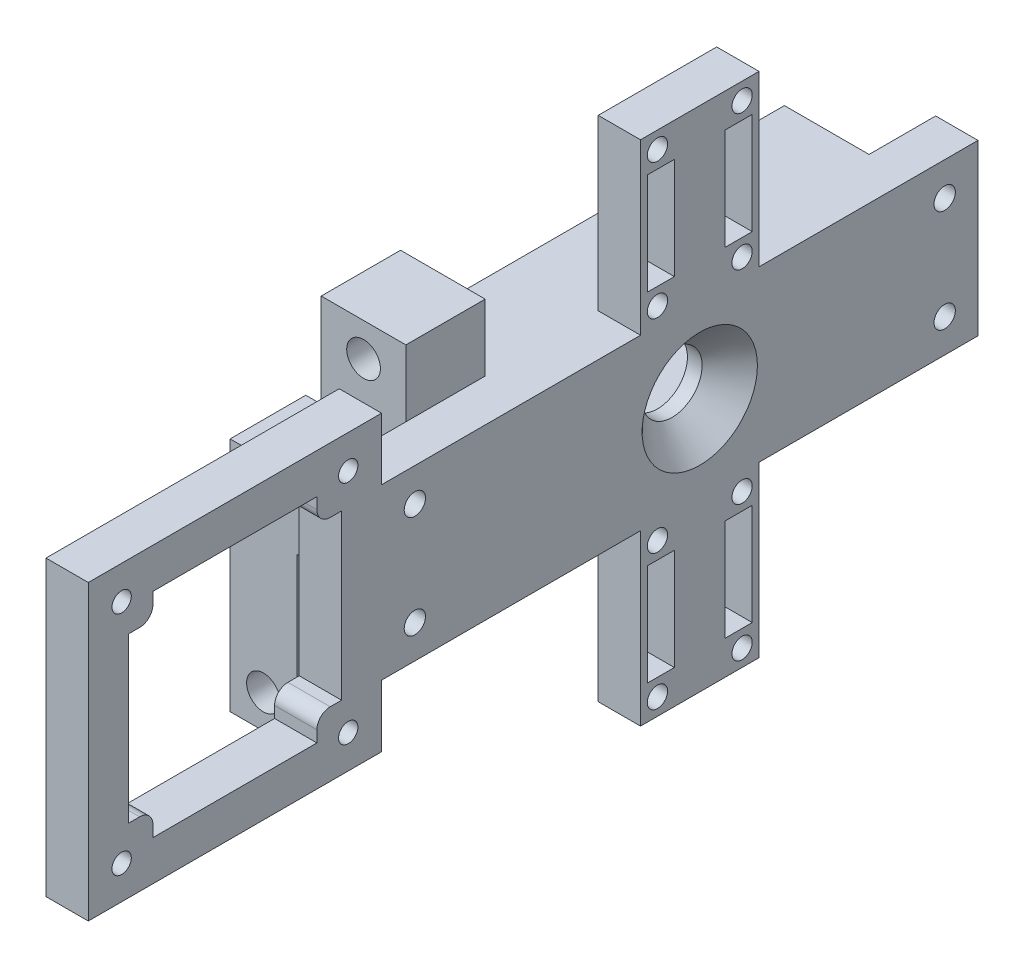
SolidWorks part; units mm, degrees
ref_plane "Front Plane" through (0, 0, 0) normal (0, 0, 1) x (1, 0, 0)
ref_plane "Top Plane" through (0, 0, 0) normal (0, 1, 0) x (1, 0, 0)
ref_plane "Right Plane" through (0, 0, 0) normal (1, 0, 0) x (0, 0, -1)
sketch "Sketch1" plane through (0, 0, 0) normal (0, 1, 0) x (1, 0, 0)
  line L1 (0, 0) -> (6.35, 0)
  line L2 (0, 0) -> (0, 89.5)
  line L3 (0, 89.5) -> (6.35, 89.5)
  line L4 (6.35, 0) -> (6.35, 89.5)
  dimension "D1" = 89.5
  dimension "D2" = 6.35
extrude "Boss-Extrude1" add sketch "Sketch1" along normal blind 25.4
sketch "Sketch2" plane through (0, 0, 0) normal (-1, 0, 0) x (0, 0, 1)
  line L0 (-89.5, 25.4) -> (0, 25.4) construction
  line L1 (-74.15, 20.05) -> (-21.35, 20.05)
  line L2 (-74.15, 20.05) -> (-74.15, 5.35)
  line L3 (-74.15, 5.35) -> (-21.35, 5.35)
  line L4 (-21.35, 20.05) -> (-21.35, 5.35)
  line L6 (-89.5, 25.4) -> (-89.5, 0) construction
  line L13 (-89.5, 0) -> (0, 0) construction
  line L14 (-79.5, 25.4) -> (-10, 25.4)
  line L15 (-79.5, 25.4) -> (-79.5, 0)
  line L16 (-79.5, 0) -> (-10, 0)
  line L17 (-10, 25.4) -> (-10, 0)
  line L18 (0, 25.4) -> (0, 0) construction
  dimension "D1" = 52.8
  dimension "D2" = 14.7
  dimension "D3" = 5.35
  dimension "D4" = 15.35
  dimension "D5" = 10
  dimension "D6" = 10
sketch "Sketch4" plane through (6.35, 0, 0) normal (1, 0, 0) x (0, 0, -1)
  line L0 (0, 25.4) -> (0, 0) construction
  line L1 (0, 34.7) -> (-44, 34.7)
  line L2 (0, 34.7) -> (0, -9.3)
  line L3 (0, -9.3) -> (-44, -9.3)
  line L4 (-44, 34.7) -> (-44, -9.3)
  line L6 (0, 25.4) -> (89.5, 25.4) construction
  circle A0 centre (-39, 29.7) radius 1.45
  circle A1 centre (-5, 29.7) radius 1.45
  circle A2 centre (-39, -4.3) radius 1.45
  circle A3 centre (-5, -4.3) radius 1.45
  dimension "D4" = 34
  dimension "D6" = 2.9
  dimension "D7" = 34
  dimension "D1" = 44
  dimension "D2" = 9.3
  dimension "D3" = 44
  dimension "D5" = 5
  dimension "D8" = 5
extrude "Boss-Extrude2" add sketch "Sketch4" against normal up to surface (6.35 mm away) up to face at (0, 12.7, -44.75)
hole_wizard "CSK for M8 Flat Head Machine Screw1" positions "Sketch6" profile "Sketch7" countersink size "M8" standard "ANSI Metric"
sketch "Sketch6" plane through (6.35, 0, 0) normal (1, 0, 0) x (0, 0, -1)
  line L1 (89.5, 25.4) -> (89.5, 0) construction
  line L2 (0, 25.4) -> (89.5, 25.4) construction
  point P0 (47.75, 12.7)
  dimension "D1" = 41.75
  dimension "D2" = 12.7
sketch "Sketch7" plane through (6.35, 12.7, -47.75) normal (0, 1, 0) x (0, 0, -1)
  line L0 (0, 0) -> (0, 20.2039)
  line L1 (0, 20.2039) -> (4.5, 17.5)
  line L2 (4.5, 17.5) -> (4.5, 4.15)
  line L3 (4.5, 4.15) -> (8.65, 0)
  line L5 (8.65, 0) -> (0, 0)
  line L6 (-4.5, 4.15) -> (-8.65, 0) construction
  line L10 (0, 20.2039) -> (-4.5, 17.5) construction
  line L11 (0, -6.35) -> (0, 107.95) construction
  dimension "Hole Dia." = 9
  dimension "Hole Depth" = 17.5
  dimension "Near C'Sink Dia." = 17.3
  dimension "Near C'Sink Angle" = 90
  dimension "Drill Angle" = 118
extrude "Boss-Extrude3" add sketch "Sketch2" along normal blind 12.7
sketch "Sketch9" plane through (0, 0, 0) normal (-1, 0, 0) x (0, 0, 1)
  line L1 (0, 34.7) -> (0, 25.4) construction
  line L2 (-10, 25.4) -> (0, 25.4) construction
  line L3 (-10, 0) -> (0, 0) construction
  line L4 (-89.5, 25.4) -> (-89.5, 0) construction
  circle A0 centre (-5, 20.4) radius 1.6
  circle A1 centre (-5, 5) radius 1.6
  circle A3 centre (-84.5, 5) radius 1.6
  circle A4 centre (-84.5, 20.4) radius 1.6
  dimension "D1" = 3.2
  dimension "D2" = 5
  dimension "D3" = 5
  dimension "D4" = 5
  dimension "D5" = 5
extrude "Cut-Extrude1" cut sketch "Sketch9" against normal up to surface (6.35 mm away) up to face at (6.35, 12.7, -56.4)
sketch "Sketch10" plane through (6.35, 0, 0) normal (1, 0, 0) x (0, 0, -1)
  line L0 (0, 25.4) -> (89.5, 25.4) construction
  line L1 (38.86, 25.4) -> (56.64, 25.4)
  line L2 (38.86, 25.4) -> (38.86, 50.8)
  line L3 (38.86, 50.8) -> (56.64, 50.8)
  line L4 (56.64, 25.4) -> (56.64, 50.8)
  line L5 (89.5, 25.4) -> (89.5, 0) construction
  line L7 (0, 0) -> (89.5, 0) construction
  line L8 (38.86, 0) -> (56.64, 0)
  line L9 (38.86, 0) -> (38.86, -25.4)
  line L10 (38.86, -25.4) -> (56.64, -25.4)
  line L11 (56.64, 0) -> (56.64, -25.4)
  circle A0 centre (41.4, 27.94) radius 1.524
  circle A1 centre (54.1, 27.94) radius 1.524
  circle A2 centre (54.1, 48.26) radius 1.524
  circle A3 centre (41.4, 48.26) radius 1.524
  circle A4 centre (41.4, -2.54) radius 1.524
  circle A5 centre (54.1, -2.54) radius 1.524
  circle A6 centre (41.4, -22.86) radius 1.524
  circle A7 centre (54.1, -22.86) radius 1.524
  point P25 (47.75, 50.8)
  dimension "D3" = 3.048
  dimension "D11" = 2.54
  dimension "D1" = 25.4
  dimension "D2" = 17.78
  dimension "D4" = 20.32
  dimension "D5" = 12.7
  dimension "D6" = 2.54
  dimension "D7" = 2.54
  dimension "D8" = 41.75
  dimension "D9" = 25.4
  dimension "D10" = 17.78
  dimension "D12" = 20.32
extrude "Boss-Extrude4" add sketch "Sketch10" against normal blind 6.35
sketch "Sketch11" plane through (6.35, 0, 0) normal (1, 0, 0) x (0, 0, -1)
  line L0 (0, 0) -> (38.86, 0) construction
  line L1 (39.876, -5.08) -> (43.94, -5.08)
  line L2 (39.876, -5.08) -> (39.876, -20.32)
  line L3 (39.876, -20.32) -> (43.94, -20.32)
  line L4 (43.94, -5.08) -> (43.94, -20.32)
  line L5 (51.56, -5.08) -> (55.624, -5.08)
  line L6 (51.56, -5.08) -> (51.56, -20.32)
  line L7 (51.56, -20.32) -> (55.624, -20.32)
  line L8 (55.624, -5.08) -> (55.624, -20.32)
  line L9 (38.86, -25.4) -> (56.64, -25.4) construction
  line L10 (38.86, 0) -> (38.86, -25.4) construction
  line L11 (56.64, -25.4) -> (56.64, 0) construction
  line L12 (56.64, 50.8) -> (38.86, 50.8) construction
  line L13 (39.876, 45.72) -> (43.94, 45.72)
  line L14 (39.876, 45.72) -> (39.876, 30.48)
  line L15 (39.876, 30.48) -> (43.94, 30.48)
  line L16 (43.94, 45.72) -> (43.94, 30.48)
  line L17 (51.56, 45.72) -> (55.624, 45.72)
  line L18 (51.56, 45.72) -> (51.56, 30.48)
  line L19 (51.56, 30.48) -> (55.624, 30.48)
  line L20 (55.624, 45.72) -> (55.624, 30.48)
  line L21 (0, 25.4) -> (38.86, 25.4) construction
  dimension "D1" = 5.08
  dimension "D2" = 5.08
  dimension "D3" = 1.016
  dimension "D4" = 4.064
  dimension "D5" = 1.016
  dimension "D6" = 5.08
  dimension "D7" = 5.08
extrude "Cut-Extrude2" cut sketch "Sketch11" against normal up to surface (6.35 mm away) up to face at (0, -22.86, -55.624)
sketch "Sketch14" plane through (0, 25.4, 0) normal (0, 1, 0) x (1, 0, 0)
  line L0 (-12.7, 10) -> (-12.7, 79.5) construction
  line L1 (0, 10) -> (-12.7, 10)
  line L2 (0, 10) -> (0, 21.9)
  line L3 (0, 21.9) -> (-12.7, 21.9)
  line L4 (-12.7, 10) -> (-12.7, 21.9)
  dimension "D1" = 11.9
extrude "Boss-Extrude5" add sketch "Sketch14" along normal blind 10
sketch "Sketch15" plane through (0, 0, -10) normal (0, 0, 1) x (1, 0, 0)
  line L0 (-12.7, 0) -> (-12.7, 35.4) construction
  line L1 (-12.7, 35.4) -> (0, 35.4) construction
  circle A0 centre (-6.35, 30.4) radius 2.5273
  dimension "D1" = 6.35
  dimension "D2" = 5.0546
  dimension "D3" = 5
extrude "Cut-Extrude4" cut sketch "Sketch15" against normal blind 7
sketch "Sketch16" plane through (-12.7, 0, 0) normal (-1, 0, 0) x (0, 0, 1)
  line L0 (-10, 0) -> (-10, 35.4) construction
  line L1 (-10, 10) -> (-21.35, 10)
  line L2 (-10, 10) -> (-10, 0)
  line L3 (-10, 0) -> (-21.35, 0)
  line L4 (-21.35, 10) -> (-21.35, 0)
  line L5 (-79.5, 0) -> (-10, 0) construction
  dimension "D1" = 10
  dimension "D2" = 11.35
extrude "Boss-Extrude6" add sketch "Sketch16" along normal blind 13.6718
sketch "Sketch17" plane through (0, 0, 0) normal (0, -1, 0) x (1, 0, 0)
  line L0 (-26.3718, -21.35) -> (-12.7, -21.35) construction
  line L1 (-26.3718, -10) -> (-16.3718, -10)
  line L2 (-26.3718, -10) -> (-26.3718, -21.35)
  line L3 (-26.3718, -21.35) -> (-16.3718, -21.35)
  line L4 (-16.3718, -10) -> (-16.3718, -21.35)
  dimension "D1" = 10
extrude "Boss-Extrude7" add sketch "Sketch17" along normal blind 25.4523
sketch "Sketch18" plane through (0, 0, -10) normal (0, 0, 1) x (1, 0, 0)
  line L0 (-16.3718, -25.4523) -> (-26.3718, -25.4523) construction
  line L1 (-26.3718, -25.4523) -> (-26.3718, 10) construction
  circle A0 centre (-21.3718, -20.4523) radius 2.5273
  circle A1 centre (-6.35, 30.4) radius 2.5273 construction
  dimension "D1" = 5
  dimension "D2" = 5
extrude "Cut-Extrude5" cut sketch "Sketch18" against normal blind 7
sketch "Sketch19" plane through (0, 0, 0) normal (0, -1, 0) x (1, 0, 0)
  line L0 (-12.7, -79.5) -> (-12.7, -21.35) construction
  line L1 (-12.7, -47.925) -> (-18.0384, -47.925)
  line L2 (-12.7, -47.925) -> (-12.7, -57.925)
  line L3 (-12.7, -57.925) -> (-18.0384, -57.925)
  line L4 (-18.0384, -47.925) -> (-18.0384, -57.925)
  line L5 (-16.3718, -21.35) -> (-12.7, -21.35) construction
  dimension "D1" = 10
  dimension "D2" = 26.575
  dimension "D3" = 5.3384
extrude "Boss-Extrude8" add sketch "Sketch19" against normal up to surface (5.35 mm away) up to face at (-6.35, 5.35, -47.75)
sketch "Sketch21" plane through (0, 0, 0) normal (0, -1, 0) x (1, 0, 0)
  line L1 (-24.32, -39.85) -> (-14.32, -39.85)
  line L2 (-24.32, -39.85) -> (-24.32, -49.85)
  line L3 (-24.32, -49.85) -> (-14.32, -49.85)
  line L4 (-14.32, -39.85) -> (-14.32, -49.85)
  line L5 (-16.9785, -23.35) -> (-8.8616, -23.35)
  line L6 (-16.9785, -23.35) -> (-16.9785, -28.35)
  line L7 (-16.9785, -28.35) -> (-8.8616, -28.35)
  line L8 (-8.8616, -23.35) -> (-8.8616, -28.35)
  line L10 (-16.9785, -61.35) -> (-8.8616, -61.35)
  line L11 (-16.9785, -61.35) -> (-16.9785, -66.35)
  line L12 (-16.9785, -66.35) -> (-8.8616, -66.35)
  line L13 (-8.8616, -61.35) -> (-8.8616, -66.35)
  line L17 (-16.3718, -21.35) -> (-12.7, -21.35) construction
  line L18 (-12.7, -47.925) -> (-12.7, -21.35) construction
  point P12 (-14.32, -44.85)
  point P19 (-19.32, -39.85)
  dimension "D1" = 21.5
  dimension "D2" = 10.4584
  dimension "D3" = 5
  dimension "D4" = 43
  dimension "D5" = 5
  dimension "D6" = 10
  dimension "D7" = 8.1169
  dimension "D8" = 10
  dimension "D9" = 2
  dimension "D10" = 3.8384
extrude "Boss-Extrude9" add sketch "Sketch21" along normal blind 11.85
sketch "Sketch22" plane through (0, -11.85, 0) normal (0, -1, 0) x (1, 0, 0)
  line L2 (-14.32, -49.85) -> (-14.32, -39.85) construction
  line L3 (-24.32, -49.85) -> (-14.32, -49.85) construction
  circle A1 centre (-19.32, -44.85) radius 2.5273
  point P6 (0, 0)
  dimension "D1" = 5.0546
  dimension "D3" = 5
  dimension "D2" = 5
extrude "Cut-Extrude6" cut sketch "Sketch22" against normal blind 7
sketch "Sketch25" plane through (-18.0384, 0, 0) normal (-1, 0, 0) x (0, 0, 1)
  line L5 (-47.925, 5.35) -> (-47.925, 0) construction
  line L6 (-57.925, 5.35) -> (-47.925, 5.35)
  line L7 (-57.925, 5.35) -> (-57.925, 0)
  line L8 (-57.925, 0) -> (-47.925, 0)
  line L9 (-47.925, 5.35) -> (-47.925, 0)
  line L10 (-56.64, 0) -> (-38.86, 0) construction
extrude "Cut-Extrude7" cut sketch "Sketch25" against normal up to surface (5.3384 mm away) up to face at (-12.7, 1.7833, -31.7083)
sketch "Sketch26" plane through (6.35, 0, 0) normal (1, 0, 0) x (0, 0, -1)
  line L23 (-34.3, 28.7) -> (-9.7, 28.7)
  line L26 (-38, 25) -> (-38, 0.4)
  line L27 (-34.3, -3.3) -> (-9.7, -3.3)
  line L28 (-6, 25) -> (-6, 0.4)
  line L30 (-44, 34.7) -> (-44, -9.3) construction
  line L31 (-44, -9.3) -> (0, -9.3) construction
  line L33 (-34.3, 28.7) -> (-34.3, 25)
  line L34 (-38, 25) -> (-34.3, 25)
  line L35 (-9.7, 28.7) -> (-9.7, 25)
  line L36 (-9.7, 25) -> (-6, 25)
  line L37 (-6, 0.4) -> (-9.7, 0.4)
  line L38 (-9.7, 0.4) -> (-9.7, -3.3)
  line L39 (-38, 0.4) -> (-34.3, 0.4)
  line L40 (-34.3, 0.4) -> (-34.3, -3.3)
  line L41 (0, 25.4) -> (0, 34.7) construction
  line L42 (0, 34.7) -> (-44, 34.7) construction
  dimension "D5" = 3.7
  dimension "D6" = 3.7
  dimension "D9" = 3.7
  dimension "D11" = 3.7
  dimension "D7" = 6
  dimension "D2" = 3.7
  dimension "D3" = 6
  dimension "D4" = 6
  dimension "D8" = 3.7
  dimension "D10" = 3.7
  dimension "D12" = 6
extrude "Cut-Extrude8" cut sketch "Sketch26" against normal up to surface (6.35 mm away) up to face at (0, 5, -3.4)
fillet "Fillet1" radius 2 4 edges at (3.175, 25, 9.7) (3.175, 0.4, 34.3) (3.175, 0.4, 9.7) (3.175, 25, 34.3)
sketch "Sketch27" plane through (-14.32, 0, 0) normal (1, 0, 0) x (0, 0, -1)
  line L1 (39.85, 0) -> (49.85, 0)
  line L2 (39.85, 0) -> (39.85, -11.85)
  line L3 (39.85, -11.85) -> (49.85, -11.85)
  line L4 (49.85, 0) -> (49.85, -11.85)
  point P4 (40.7733, -2.1607)
extrude "Boss-Extrude10" add sketch "Sketch27" along normal blind 5
equation "\"D1@Cut-Extrude4\"=4"
